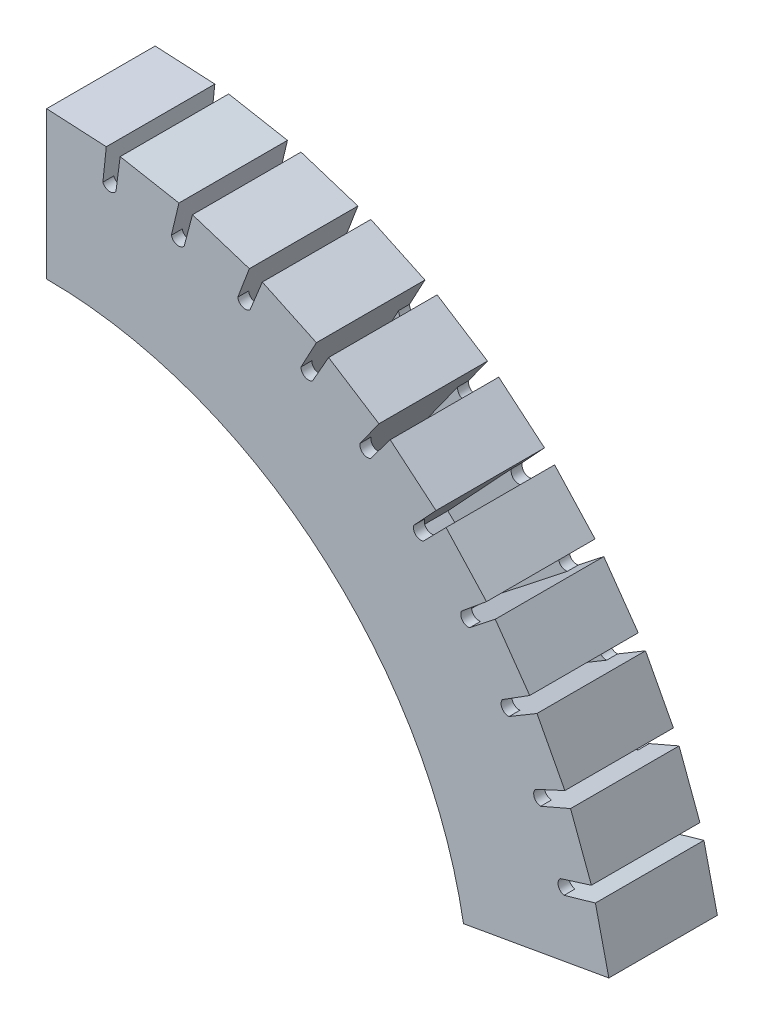
SolidWorks part; units mm, degrees
ref_plane "Ebene vorne" through (0, 0, 0) normal (0, 0, 1) x (1, 0, 0)
ref_plane "Ebene oben" through (0, 0, 0) normal (0, 1, 0) x (1, 0, 0)
ref_plane "Ebene rechts" through (0, 0, 0) normal (1, 0, 0) x (0, 0, -1)
sketch "Skizze1" plane through (0, 0, 0) normal (0, 0, 1) x (1, 0, 0)
  line L0 (0, 40) -> (0, 0) construction
  line L1 (0, 0) -> (39.3923, 6.9459) construction
  line L2 (0, 41) -> (0, 40)
  line L3 (40.3771, 7.1196) -> (39.3923, 6.9459)
  arc A0 (0, 40) -> (39.3923, 6.9459) centre (0, 0) cw
  arc A1 (0, 41) -> (40.3771, 7.1196) centre (0, 0) cw
  dimension "D1" = 40
  dimension "D2" = 1
  dimension "D3" = 80
extrude "Aufsatz-Linear austragen1" add sketch "Skizze1" along normal mid plane 10
sketch "Skizze2" plane through (0, 0, 0) normal (0, 0, 1) x (1, 0, 0)
  line L0 (0, 41) -> (0, 52.6)
  line L1 (0, 52.6) -> (5.4982, 52.3119)
  line L2 (5.4982, 52.3119) -> (4.2857, 40.7754)
  line L3 (1.8606, 35.5018) -> (-2612.3549, -49846.7015) construction
  line L4 (0, 41) -> (4.2857, 40.7754)
  arc A0 (40.3771, 7.1196) -> (0, 41) centre (0, 0) ccw construction
  arc A1 (40.3771, 7.1196) -> (0, 41) centre (0, 0) ccw construction
  arc A2 (0, 41) -> (4.2857, 40.7754) centre (0, 0) cw
  point P7 (2.1458, 40.9438)
  point P9 (2.7491, 52.4559)
  point P11 (2.1428, 40.8877)
  point P12 (0, 38.8974)
  dimension "D1" = 11.6
  dimension "D2" = 6
extrude "Aufsatz-Linear austragen2" add sketch "Skizze2" along normal mid plane 10 contours L0 A2 L2 L1 region at (2.4594, 46.9278, 0)
ref_axis "Achse1" through (0, 0, -5.5) along (0, 0, 1)
pattern_circular "Kreismuster1" count 11 every 7.4 about axis through (0, 0, -5.5) along (0, 0, 1) of "Aufsatz-Linear austragen2" reverse direction yes
sketch "Skizze3" plane through (0, 0, 0) normal (0, 0, 1) x (1, 0, 0)
  line L0 (0, 40) -> (0, 39)
  line L1 (39.3923, 6.9459) -> (38.4075, 6.7723)
  line L2 (0, 0) -> (38.4075, 6.7723)
  line L3 (0, 39) -> (0, 0) construction
  arc A0 (39.3923, 6.9459) -> (0, 40) centre (0, 0) ccw construction
  arc A1 (39.3923, 6.9459) -> (0, 40) centre (0, 0) ccw
  arc A2 (38.4075, 6.7723) -> (0, 39) centre (0, 0) ccw
  dimension "D1" = 1
extrude "Aufsatz-Linear austragen3" add sketch "Skizze3" along normal mid plane 10 contours A2 L1 A1 L0 region at (25.3802, 30.247, 0)
sketch "Skizze4" plane through (0, 0, -5) normal (0, 0, -1) x (-1, 0, 0)
  line L0 (-47.6784, 13.6716) -> (-39.4117, 11.3011)
  line L1 (-39.4117, 11.3011) -> (-50.5624, 14.4985) construction
  line L2 (-39.4117, 11.3011) -> (-39.1239, 12.2607)
  line L3 (-39.1239, 12.2607) -> (-47.3301, 14.8324)
  line L4 (-50.193, 15.7295) -> (-39.1239, 12.2607) construction
  line L5 (-47.3301, 14.8324) -> (-47.6784, 13.6716) construction
  line L6 (-46.0504, 13.8158) -> (47845.0739, -14354.2101) construction
  line L7 (-50.193, 15.7295) -> (-50.5624, 14.4985) construction
  arc A0 (-47.3301, 14.8324) -> (-47.6784, 13.6716) centre (-47.8025, 14.3414) cw
  point P5 (-47.5042, 14.252)
  point P14 (-39.2678, 11.7809)
  point P15 (-47.8025, 14.3414)
  point P16 (0, 0)
  dimension "D1" = 3
extrude "Aufsatz-Linear austragen4" add sketch "Skizze4" against normal blind 1
mirror "Spiegeln1" about plane through (0, 0, 0) normal (0, 0, 1) of "Aufsatz-Linear austragen4"
pattern_circular "Kreismuster2" count 10 every 7.4 about axis through (0, 0, -5.5) along (0, 0, 1) of "Spiegeln1", "Aufsatz-Linear austragen4"
